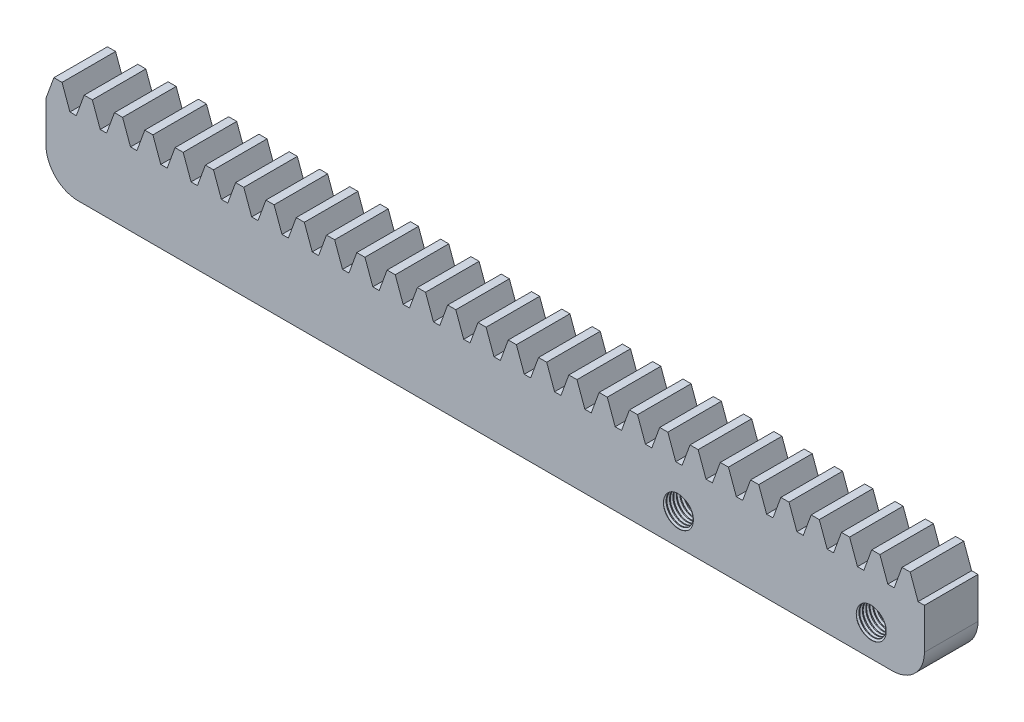
SolidWorks part; units mm, degrees
material "1.1193 (C45G)"
ref_plane "Front" through (0, 0, 0) normal (0, 0, 1) x (1, 0, 0)
ref_plane "Top" through (0, 0, 0) normal (0, 1, 0) x (1, 0, 0)
ref_plane "Right" through (0, 0, 0) normal (1, 0, 0) x (0, 0, -1)
sketch "Sketch1" plane through (0, 0, 0) normal (0, 0, 1) x (1, 0, 0)
  line L1 (0, 0) -> (81.9956, 0)
  line L2 (0, 0) -> (0, -8)
  line L3 (0, -8) -> (81.9956, -8)
  line L4 (81.9956, 0) -> (81.9956, -8)
  dimension "D1" = 8
  dimension "L" = 81.9956
extrude "Extrude1" add sketch "Sketch1" along normal blind 5
sketch "Sketch2" plane through (0, 0, 5) normal (0, 0, 1) x (1, 0, 0)
  line L0 (0, 0) -> (0.737, 2.025)
  line L1 (0.737, 2.025) -> (1.4956, 2.025)
  line L2 (1.4956, 2.025) -> (2.2326, 0)
  line L3 (81.9956, 0) -> (0, 0) construction
  line L4 (0, 0) -> (2.2326, 0)
  line L5 (0.4095, 1.125) -> (1.8232, 1.125) construction
  dimension "alpha2" = 70
  dimension "alpha" = 110
  dimension "ha" = 0.9
  dimension "hf" = 1.125
  dimension "S" = 1.4137
extrude "Extrude2" add sketch "Sketch2" against normal up to surface (5 mm away) up to face at (40.9978, -4, 0)
pattern_linear "LPattern1" count 29 spacing 2.8274 along (1, 0, 0) of "Extrude2"
sketch "草图1" plane through (0, -8, 0) normal (0, -1, 0) x (1, 0, 0)
  line L4 (0, 0) -> (81.9956, 0)
  line L5 (81.9956, 0) -> (81.9956, 5)
  line L6 (81.9956, 5) -> (0, 5)
  line L7 (0, 5) -> (0, 0)
  line L8 (0, 0) -> (81.9956, 0)
  line L9 (81.9956, 0) -> (81.9956, 5)
  line L10 (81.9956, 5) -> (0, 5)
  line L11 (0, 5) -> (0, 0)
  dimension "D1" = 0
extrude "切除-拉伸1" cut sketch "草图1" against normal blind 1.2
sketch "草图3" plane through (0, 0, 5) normal (0, 0, 1) x (1, 0, 0)
  circle A0 centre (76.9956, -3.8) radius 1.5 construction
  circle A1 centre (58.9956, -3.8) radius 1.5 construction
  circle A2 centre (76.9956, -3.8) radius 1.5
  circle A3 centre (58.9956, -3.8) radius 1.5
extrude "切除-拉伸2" cut sketch "草图3" against normal through all
fillet "圆角1" radius 3 2 edges at (81.9956, -6.8, 2.5) (0, -6.8, 2.5)
thread "螺纹线1" pitch 0.3175 method extrude trim with end face yes profile "螺纹线轮廓1" start angle 0, offset 0, length 5, pitch 0.3175, diameter 3
ref_plane "基准面1" through (78.4956, -3.8, 0) normal (0, -1, 0) x (1, 0, 0)
sketch "螺纹线轮廓1" plane through (78.4956, -3.8, 0) normal (0, -1, 0) x (1, 0, 0)
  line L0 (0, 0) -> (0, 0.3175) construction
  line L11 (0, 0) -> (0, 0.2778)
  line L12 (0, 0.2778) -> (-0.1719, 0.1786)
  line L13 (-0.1719, 0.1786) -> (-0.1719, 0.0992)
  line L15 (-0.1719, 0.0992) -> (0, 0)
  line L17 (-0.1719, 0.1389) -> (0, 0.1389) construction
  point P2 (0, 0)
  dimension "Pitch" = 0.3175
  dimension "Profile_Angle" = 60
  dimension "Profile_Land" = 0.0794
  dimension "Profile_Height" = 0.1719
thread "螺纹线2" pitch 0.3175 method extrude trim with end face yes profile "螺纹线轮廓3" start angle 0, offset 0, length 5, pitch 0.3175, diameter 3
ref_plane "基准面3" through (60.4956, -3.8, 0) normal (0, -1, 0) x (1, 0, 0)
sketch "螺纹线轮廓3" plane through (60.4956, -3.8, 0) normal (0, -1, 0) x (1, 0, 0)
  line L0 (0, 0) -> (0, 0.3175) construction
  line L11 (0, 0) -> (0, 0.2778)
  line L12 (0, 0.2778) -> (-0.1719, 0.1786)
  line L13 (-0.1719, 0.1786) -> (-0.1719, 0.0992)
  line L15 (-0.1719, 0.0992) -> (0, 0)
  line L17 (-0.1719, 0.1389) -> (0, 0.1389) construction
  point P2 (0, 0)
  dimension "Pitch" = 0.3175
  dimension "Profile_Angle" = 60
  dimension "Profile_Land" = 0.0794
  dimension "Profile_Height" = 0.1719
